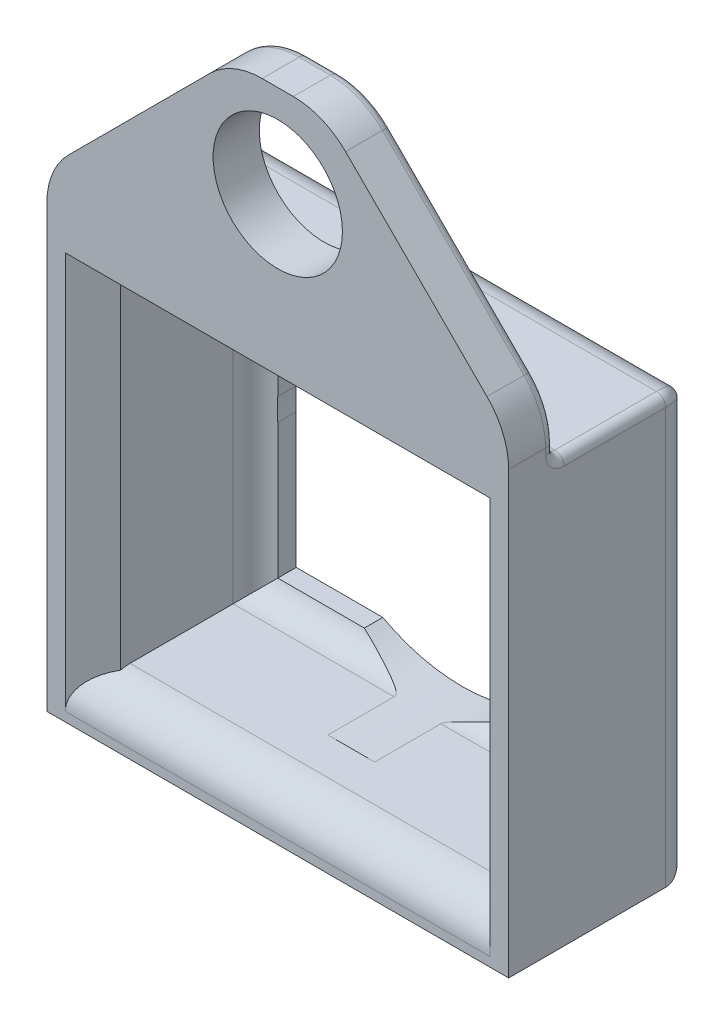
SolidWorks part; units mm, degrees
ref_plane "Front Plane" through (0, 0, 0) normal (0, 0, 1) x (1, 0, 0)
ref_plane "Top Plane" through (0, 0, 0) normal (0, 1, 0) x (1, 0, 0)
ref_plane "Right Plane" through (0, 0, 0) normal (1, 0, 0) x (0, 0, -1)
sketch "Sketch1" plane through (0, 0, 0) normal (0, 0, 1) x (1, 0, 0)
  line L1 (-22.1127, 40.5634) -> (27.8873, 40.5634)
  line L2 (-22.1127, 40.5634) -> (-22.1127, -5.4366)
  line L3 (-22.1127, -5.4366) -> (27.8873, -5.4366)
  line L4 (27.8873, 40.5634) -> (27.8873, -5.4366)
  dimension "D1" = 50
  dimension "D2" = 46
extrude "Boss-Extrude1" add sketch "Sketch1" along normal blind 20
sketch "Sketch6" plane through (0, 40.5634, 0) normal (0, 1, 0) x (1, 0, 0)
  line L0 (-22.1127, -20) -> (-22.1127, 0) construction
  line L1 (-22.1127, -15) -> (27.8873, -15)
  line L2 (-22.1127, -15) -> (-22.1127, -20)
  line L3 (-22.1127, -20) -> (27.8873, -20)
  line L4 (27.8873, -15) -> (27.8873, -20)
  line L5 (27.8873, -20) -> (27.8873, 0) construction
  line L6 (27.8873, -20) -> (-22.1127, -20) construction
  dimension "D1" = 5
extrude "Boss-Extrude4" add sketch "Sketch6" along normal blind 25
sketch "Sketch7" plane through (0, 0, 20) normal (0, 0, 1) x (1, 0, 0)
  line L0 (27.8873, -5.4366) -> (27.8873, 65.5634) construction
  line L1 (-22.1127, 65.5634) -> (27.8873, 65.5634) construction
  circle A0 centre (2.8873, 55.5634) radius 7
  dimension "D2" = 14
  dimension "D1" = 25
  dimension "D3" = 10
extrude "Cut-Extrude5" cut sketch "Sketch7" against normal blind 20
fillet "Fillet3" radius 1 1 edges at (2.8873, 40.5634, 15)
sketch "Sketch8" plane through (0, 0, 20) normal (0, 0, 1) x (1, 0, 0)
  line L0 (-22.1127, -5.4366) -> (27.8873, -5.4366) construction
  line L1 (-17.1127, -0.4366) -> (22.8873, -0.4366)
  line L2 (-17.1127, -0.4366) -> (-17.1127, 35.5634)
  line L3 (-17.1127, 35.5634) -> (22.8873, 35.5634)
  line L4 (22.8873, -0.4366) -> (22.8873, 35.5634)
  line L5 (27.8873, -5.4366) -> (27.8873, 65.5634) construction
  line L6 (-22.1127, 65.5634) -> (-22.1127, -5.4366) construction
  dimension "D1" = 5
  dimension "D2" = 5
  dimension "D3" = 5
  dimension "D4" = 36
extrude "Cut-Extrude6" cut sketch "Sketch8" against normal blind 18
sketch "Sketch9" plane through (0, 0, 2) normal (0, 0, 1) x (1, 0, 0)
  line L0 (22.8873, 35.5634) -> (-17.1127, 35.5634) construction
  line L1 (-15.1127, 33.5634) -> (20.8873, 33.5634)
  line L2 (-15.1127, 33.5634) -> (-15.1127, 1.5634)
  line L3 (-15.1127, 1.5634) -> (20.8873, 1.5634)
  line L4 (20.8873, 33.5634) -> (20.8873, 1.5634)
  line L5 (-17.1127, -0.4366) -> (22.8873, -0.4366) construction
  line L6 (22.8873, -0.4366) -> (22.8873, 35.5634) construction
  line L7 (-17.1127, 35.5634) -> (-17.1127, -0.4366) construction
  dimension "D1" = 2
  dimension "D2" = 2
  dimension "D3" = 2
  dimension "D4" = 2
extrude "Cut-Extrude7" cut sketch "Sketch9" against normal blind 12
chamfer "Chamfer1" distance 20 angle 45 2 edges at (27.8873, 65.5634, 17.5) (-22.1127, 65.5634, 17.5)
fillet "Fillet4" radius 4 1 edges at (2.8873, -0.4366, 20)
chamfer "Chamfer2" distance 3 angle 45 3 edges at (-17.1127, 15.5634, 20) (22.8873, 15.5634, 20) (2.8873, 35.5634, 20)
fillet "Fillet5" radius 3 4 edges at (22.8873, 17.5634, 2) (2.8873, -0.4366, 2) (-17.1127, 17.5634, 2) (2.8873, 35.5634, 2)
sketch "Sketch10" plane through (0, 0, 0) normal (0, 0, -1) x (-1, 0, 0)
  circle A0 centre (-2.8459, 17.384) radius 18
  point P2 (-2.9703, 17.3011)
  point P3 (-2.8459, 17.384)
extrude "Cut-Extrude8" cut sketch "Sketch10" against normal blind 12
fillet "Fillet6" radius 8 4 edges at (27.8873, 45.5634, 17.5) (-22.1127, 45.5634, 17.5) (7.8873, 65.5634, 17.5) (-2.1127, 65.5634, 17.5)
fillet "Fillet7" radius 3 4 edges at (2.8873, -5.4366, 0) (27.8873, 17.5634, 0) (2.8873, 40.5634, 0) (-22.1127, 17.5634, 0)
fillet "Fillet8" radius 1 15 edges at (-21.234, 39.6847, 0.8787) (-22.1127, 40.5634, 8.5) (-22.1127, 40.8563, 14.7071) (-22.1127, 41.9065, 15) (-21.5037, 45.3111, 15) (27.0086, 39.6847, 0.8787) (27.8873, 40.5634, 8.5) (27.8873, 40.8563, 14.7071) (27.8873, 41.9065, 15) (27.2784, 45.3111, 15) (17.8873, 55.5634, 15) (7.6351, 64.9544, 15) (2.8873, 65.5634, 15) (-1.8604, 64.9544, 15) (-12.1127, 55.5634, 15)
